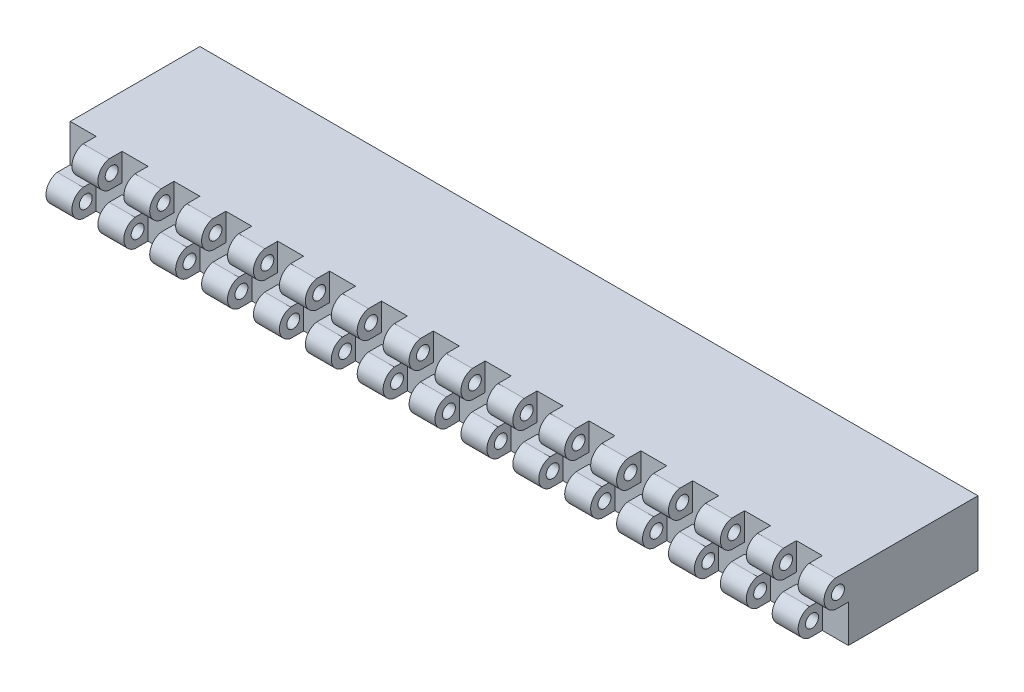
SolidWorks part; units mm, degrees
ref_plane "Front Plane" through (0, 0, 0) normal (0, 0, 1) x (1, 0, 0)
ref_plane "Top Plane" through (0, 0, 0) normal (0, 1, 0) x (1, 0, 0)
ref_plane "Right Plane" through (0, 0, 0) normal (1, 0, 0) x (0, 0, -1)
sketch "Sketch1" plane through (0, 0, 0) normal (1, 0, 0) x (0, 0, -1)
  line L1 (-25, 12.5) -> (25, 12.5)
  line L2 (-25, 12.5) -> (-25, -12.5)
  line L3 (-25, -12.5) -> (25, -12.5)
  line L4 (25, 12.5) -> (25, -12.5)
  line L5 (-25, 12.5) -> (25, -12.5) construction
  line L6 (-25, -12.5) -> (25, 12.5) construction
  point P0 (0, 0)
  dimension "D1" = 25
  dimension "D2" = 50
extrude "Boss-Extrude1" add sketch "Sketch1" along normal mid plane 300
sketch "Sketch2" plane through (150, 0, 0) normal (1, 0, 0) x (0, 0, -1)
  line L1 (-25, -12.5) -> (-25, 2) construction
  line L2 (-25, 2) -> (-25, 12.5)
  line L3 (-25, 2) -> (-30, 2)
  line L4 (-25, 12.5) -> (-30, 12.5)
  line L5 (25, 12.5) -> (-25, 12.5) construction
  arc A1 (-30, 12.5) -> (-30, 2) centre (-29, 7.25) ccw
  circle A2 centre (-29, 7.25) radius 2.5
  point P7 (-25, 7.25)
  dimension "D3" = 5
  dimension "D1" = 10.5
  dimension "D2" = 5
  dimension "D4" = 4
extrude "Boss-Extrude2" add sketch "Sketch2" against normal blind 10
pattern_linear "LPattern1" count 15 spacing 20 along (-1, 0, 0) of "Boss-Extrude2"
sketch "Sketch4" plane through (0, 0, -25) normal (0, 0, -1) x (-1, 0, 0)
  circle A0 centre (0, 0) radius 7
  dimension "D1" = 14
extrude "Cut-Extrude1" cut sketch "Sketch4" against normal blind 30
sketch "Sketch3" plane through (-150, 0, 0) normal (-1, 0, 0) x (0, 0, 1)
  line L0 (25, -12.5) -> (25, 0)
  line L1 (25, 12.5) -> (25, -12.5) construction
  line L2 (25, -12.5) -> (-25, -12.5) construction
  line L3 (25, -2) -> (30, -2)
  line L4 (25, -12.5) -> (30, -12.5)
  arc A1 (30, -12.5) -> (30, -2) centre (29, -7.25) ccw
  circle A2 centre (29, -7.25) radius 2.5
  point P7 (25, -6.25)
  dimension "D2" = 4
  dimension "D3" = 5
  dimension "D1" = 5
  dimension "D4" = 10.5
extrude "Boss-Extrude3" add sketch "Sketch3" against normal blind 10 contours L4 A1 L3 L0 A2 region at (-150, -7.25, 25.1406)
pattern_linear "LPattern2" count 15 spacing 20 along (1, 0, 0) of "Boss-Extrude3"
